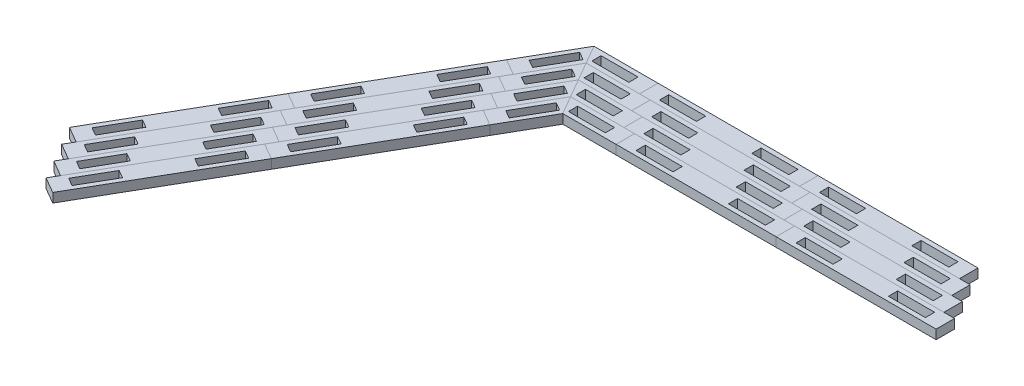
SolidWorks part; units mm, degrees
material "Cedar"
ref_plane "Front Plane" through (0, 0, 0) normal (0, 0, 1) x (1, 0, 0)
ref_plane "Top Plane" through (0, 0, 0) normal (0, 1, 0) x (1, 0, 0)
ref_plane "Right Plane" through (0, 0, 0) normal (1, 0, 0) x (0, 0, -1)
sketch "Sketch1" plane through (0, 0, 0) normal (0, 1, 0) x (1, 0, 0)
  line L0 (-54.9926, 0) -> (54.9926, 0) construction
  line L1 (-54.9926, 0) -> (0, -31.75)
  line L2 (0, -31.75) -> (54.9926, 0)
  line L3 (54.9926, 0) -> (54.9926, 63.5)
  line L4 (54.9926, 63.5) -> (0, 95.25)
  line L5 (0, 95.25) -> (-54.9926, 63.5)
  line L6 (-54.9926, 63.5) -> (-54.9926, 0)
  line L7 (0, -31.75) -> (0, 31.75) construction
  circle A0 centre (0, 31.75) radius 54.9926 construction
  point P9 (0, 0)
  dimension "D1" = 63.5
extrude "Boss-Extrude1" add sketch "Sketch1" against normal blind 6.35
sketch "Sketch2" plane through (0, 0, 0) normal (0, 1, 0) x (1, 0, 0)
  line L0 (-54.9926, 31.75) -> (54.9926, 31.75) construction
  line L1 (-54.9926, 63.5) -> (-54.9926, 0) construction
  line L2 (54.9926, 0) -> (54.9926, 63.5) construction
  point P2 (0, 31.75)
ref_axis "Axis1" through (0, 0, -31.75) along (0, 1, 0)
sketch "Sketch10" plane through (0, 0, 0) normal (0, 1, 0) x (1, 0, 0)
  line L0 (0, -31.75) -> (-16.4978, -22.225) construction
  line L1 (-16.4978, -22.225) -> (-7.8235, -19.9007)
  line L2 (-7.8235, -19.9007) -> (-24.3213, -10.3757)
  line L3 (-24.3213, -10.3757) -> (-27.4963, -15.875)
  line L4 (-16.4978, -22.225) -> (-27.4963, -15.875)
  line L5 (-54.9926, 0) -> (0, -31.75) construction
  dimension "D1" = 45
  dimension "D2" = 6.35
extrude "Cut-Extrude4" cut sketch "Sketch10" against normal through all
sketch "Sketch11" plane through (0, 0, 0) normal (0, 1, 0) x (1, 0, 0)
  line L0 (-27.4963, -15.875) -> (-54.9926, 0) construction
  line L1 (-27.4963, -15.875) -> (-30.6713, -21.3743)
  line L2 (-30.6713, -21.3743) -> (-47.1691, -11.8493)
  line L3 (-47.1691, -11.8493) -> (-38.4948, -9.525)
  line L4 (-38.4948, -9.525) -> (-27.4963, -15.875)
  line L5 (-38.4948, -9.525) -> (-54.9926, 0) construction
  line L6 (-38.4948, -9.525) -> (-54.9926, 0) construction
  line L7 (-54.9926, 0) -> (-27.4963, -15.875) construction
  line L8 (-54.9926, 63.5) -> (-54.9926, 0) construction
  dimension "D1" = 45
  dimension "D2" = 6.35
extrude "Boss-Extrude4" add sketch "Sketch11" against normal blind 6.35
pattern_circular "CirPattern1" count 2 every 60 about axis through (0, 0, -31.75) along (0, 1, 0) of "Cut-Extrude4", "Boss-Extrude4"
sketch "Sketch12" plane through (0, 0, 0) normal (0, 1, 0) x (1, 0, 0)
  line L0 (-54.9926, 12.7) -> (54.9926, 12.7)
  line L1 (-54.9926, 63.5) -> (-54.9926, 0) construction
  line L2 (54.9926, 0) -> (54.9926, 63.5) construction
  line L3 (54.9926, 12.7) -> (54.9926, 95.25)
  line L4 (54.9926, 95.25) -> (-54.9926, 95.25)
  line L5 (-54.9926, 95.25) -> (-54.9926, 12.7)
  line L6 (0, 0) -> (0, 12.7) construction
  dimension "D1" = 12.7
extrude "Cut-Extrude5" cut sketch "Sketch12" against normal through all
sketch "Sketch13" plane through (0, 0, 0) normal (0, 1, 0) x (1, 0, 0)
  line L0 (0, 0) -> (0, 12.7) construction
  line L1 (-54.9926, 12.7) -> (54.9926, 12.7) construction
  line L2 (-31.75, 6.35) -> (31.75, 6.35) construction
  line L4 (-44.45, 9.525) -> (-19.05, 9.525)
  line L5 (-44.45, 9.525) -> (-44.45, 3.175)
  line L6 (-44.45, 3.175) -> (-19.05, 3.175)
  line L7 (-19.05, 9.525) -> (-19.05, 3.175)
  line L8 (-44.45, 9.525) -> (-19.05, 3.175) construction
  line L9 (-44.45, 3.175) -> (-19.05, 9.525) construction
  line L10 (19.05, 9.525) -> (44.45, 9.525)
  line L11 (19.05, 9.525) -> (19.05, 3.175)
  line L12 (19.05, 3.175) -> (44.45, 3.175)
  line L13 (44.45, 9.525) -> (44.45, 3.175)
  line L14 (19.05, 9.525) -> (44.45, 3.175) construction
  line L15 (19.05, 3.175) -> (44.45, 9.525) construction
  point P7 (0, 6.35)
  point P8 (0, 6.35)
  dimension "D1" = 6.35
  dimension "D2" = 25.4
  dimension "D3" = 6.35
  dimension "D4" = 25.4
  dimension "D5" = 63.5
extrude "Cut-Extrude6" cut sketch "Sketch13" against normal through all
pattern_linear "LPattern1" count 5 spacing 109.9852 along (1, 0, 0) count 2 spacing 109.9852 along (-1, 0, 0) pattern seed only yes of bodies 136 131
sketch "Sketch14" plane through (0, 0, 0) normal (0, 1, 0) x (1, 0, 0)
  line L0 (439.9409, -31.75) -> (439.9409, 12.7)
  line L1 (384.9483, 12.7) -> (494.9335, 12.7) construction
  line L2 (439.9409, 12.7) -> (494.9335, 12.7)
  line L3 (494.9335, 12.7) -> (494.9335, -31.75)
  line L4 (494.9335, -31.75) -> (439.9409, -31.75)
  line L5 (-109.9852, -31.75) -> (-109.9852, 12.7)
  line L6 (-164.9778, 12.7) -> (-54.9926, 12.7) construction
  line L7 (-109.9852, 12.7) -> (-164.9778, 12.7)
  line L8 (-164.9778, 12.7) -> (-164.9778, -31.75)
  line L9 (-164.9778, -31.75) -> (-109.9852, -31.75)
  line L10 (415.6196, -10.3757) -> (428.9424, 12.7)
  line L11 (428.9424, 12.7) -> (439.9409, 12.7)
  line L12 (415.6196, -10.3757) -> (409.2696, -21.3743)
  line L13 (409.2696, -21.3743) -> (439.9409, -31.75)
  line L14 (-79.3139, -21.3743) -> (-98.9867, 12.7)
  line L15 (-98.9867, 12.7) -> (-109.9852, 12.7)
  line L16 (-79.3139, -21.3743) -> (-95.8117, -30.8993)
  line L17 (-95.8117, -30.8993) -> (-109.9852, -31.75)
  line L18 (-85.6639, -10.3757) -> (-79.3139, -21.3743) construction
  line M5 (484.3909, 9.525) -> (484.3909, 3.175)
  line M6 (484.3909, 3.175) -> (458.9909, 3.175)
  line M7 (458.9909, 3.175) -> (458.9909, 9.525)
  line M8 (458.9909, 9.525) -> (484.3909, 9.525)
  line M13 (494.9335, 12.7) -> (384.9483, 12.7)
  line M19 (415.6196, -10.3757) -> (432.1174, -19.9007)
  line M20 (432.1174, -19.9007) -> (423.4431, -22.225)
  line M21 (423.4431, -22.225) -> (439.9409, -31.75)
  line M22 (439.9409, -31.75) -> (456.4387, -22.225)
  line M23 (456.4387, -22.225) -> (454.1144, -30.8993)
  line M24 (454.1144, -30.8993) -> (470.6122, -21.3743)
  line M25 (470.6122, -21.3743) -> (464.2622, -10.3757)
  line M26 (464.2622, -10.3757) -> (480.76, -0.8507)
  line M27 (480.76, -0.8507) -> (478.4357, -9.525)
  line M28 (478.4357, -9.525) -> (494.9335, 0)
  line M29 (494.9335, 0) -> (494.9335, 12.7)
extrude "Cut-Extrude7" cut sketch "Sketch14" against normal through all contours L17 L16 L14 L15 L5 | L10 L0 M19 M20 M21 M13 | L0 M22 M23 M24 M25 M26 M27 M28 M29 M13 M8 M5 M6 M7 | L8 L9 L5 L7 region at (431.3731, 0, 7.3494) region at (460.5225, 0, 5.1278) region at (-137.4815, 0, 9.525) region at (-98.715, 0, 11.4335)
sketch "Sketch15" plane through (0, 0, 0) normal (0, 1, 0) x (1, 0, 0)
  line L0 (-222.3722, 0) -> (552.3278, 0)
  line L3 (-222.3722, 0) -> (-222.3722, -63.5)
  line L4 (-222.3722, -63.5) -> (552.3278, -63.5)
  line L5 (552.3278, -63.5) -> (552.3278, 0)
  line L6 (164.9778, 0) -> (164.9778, 12.7)
  line L7 (164.9778, 12.7) -> (552.3278, 12.7)
  line L8 (552.3278, 12.7) -> (552.3278, 0)
  point P4 (164.9778, 0)
  line M15 (-54.9926, 0) -> (-38.4948, -9.525)
  line M16 (-38.4948, -9.525) -> (-47.1691, -11.8493)
  line M17 (-47.1691, -11.8493) -> (-30.6713, -21.3743)
  line M18 (-30.6713, -21.3743) -> (-24.3213, -10.3757)
  line M19 (-24.3213, -10.3757) -> (-7.8235, -19.9007)
  line M20 (-7.8235, -19.9007) -> (-16.4978, -22.225)
  line M21 (-16.4978, -22.225) -> (0, -31.75)
  line M22 (0, -31.75) -> (16.4978, -22.225)
  line M23 (16.4978, -22.225) -> (14.1735, -30.8993)
  line M24 (14.1735, -30.8993) -> (30.6713, -21.3743)
  line M25 (30.6713, -21.3743) -> (24.3213, -10.3757)
  line M26 (24.3213, -10.3757) -> (40.8191, -0.8507)
  line M27 (40.8191, -0.8507) -> (38.4948, -9.525)
  line M28 (38.4948, -9.525) -> (54.9926, 0)
  dimension "D1" = 63.5
  dimension "D2" = 774.7
extrude "Cut-Extrude8" cut sketch "Sketch15" against normal through all contours L8 L7 L6 L0 | L4 L5 L0 L3 M28 M27 M26 M25 M24 M23 M22 M21 M20 M19 M18 M17 M16 M15 | L0 M15 M16 M17 M18 M19 M20 M21 M22 M23 M24 M25 M26 M27 M28 | L5 L0 L3 L4 region at (171.108, 0, 32.504) region at (-1.6087, 0, 11.2607) region at (358.6528, 0, -6.35)
mirror "Mirror1" about plane through (-68.7408, -6.35, 39.6875) normal (0.866, 0, -0.5) of bodies 151 149 146
pattern_linear "LPattern2" count 4 spacing 14.6647 along (0.5, 0, 0.866) of bodies 146 149 151 152 153 154
